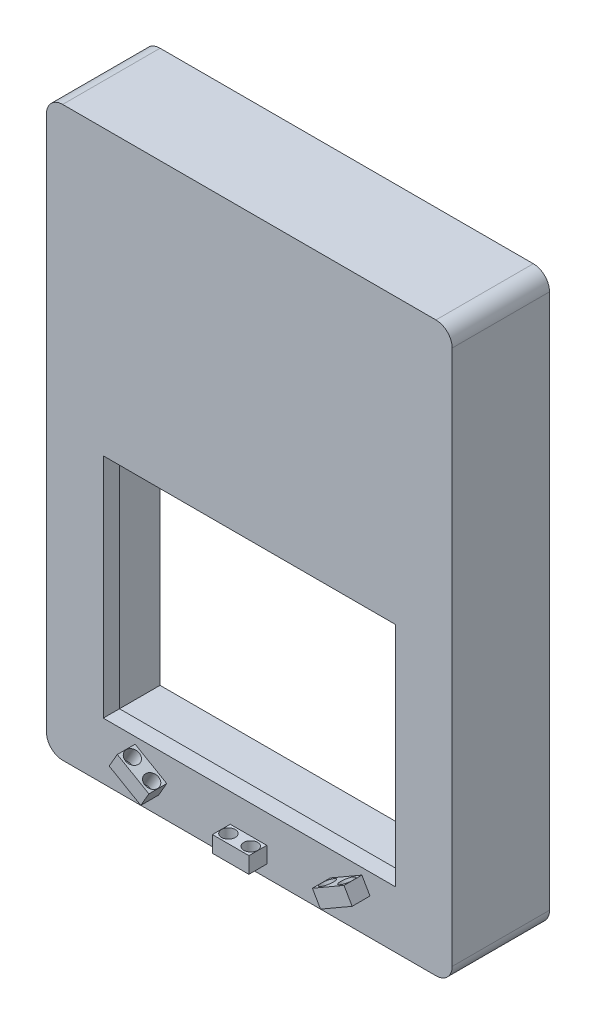
SolidWorks part; units mm, degrees
ref_plane "Piano frontale" through (0, 0, 0) normal (0, 0, 1) x (1, 0, 0)
ref_plane "Piano superiore" through (0, 0, 0) normal (0, 1, 0) x (1, 0, 0)
ref_plane "Piano destro" through (0, 0, 0) normal (1, 0, 0) x (0, 0, -1)
sketch "Schizzo1" plane through (0, 0, 0) normal (0, 0, 1) x (1, 0, 0)
  line L0 (0, 0) -> (0, -700)
  line L1 (0, 0) -> (500, 0)
  line L2 (500, 0) -> (500, -700)
  line L3 (500, -700) -> (0, -700)
  line L8 (20, -20) -> (480, -20)
  line L9 (480, -20) -> (480, -680)
  line L10 (480, -680) -> (20, -680)
  line L11 (20, -20) -> (20, -680)
  dimension "D1" = 700
  dimension "D2" = 500
  dimension "D3" = 20
extrude "Estrusione-Estrusione4" add sketch "Schizzo1" along normal blind 20 contours L3 L0 L1 L2
extrude "Estrusione-Estrusione5" add sketch "Schizzo1<4>" against normal blind 100
sketch "Schizzo1<4>" plane through (0, 0, 0) normal (0, 0, 1) x (1, 0, 0) same geometry as "Schizzo1"
sketch "Schizzo2" plane through (0, 0, 0) normal (0, 0, 1) x (1, 0, 0)
  line L4 (148.2503, -660.67) -> (138.2491, -677.9899)
  line L5 (226.5, -665) -> (271.5, -665)
  line L6 (226.5, -665) -> (226.5, -685)
  line L7 (226.5, -685) -> (271.5, -685)
  line L8 (271.5, -685) -> (271.5, -665)
  line L10 (109.2791, -638.17) -> (99.2791, -655.4905)
  line L11 (99.2791, -655.4905) -> (138.2491, -677.9899)
  line L14 (109.2791, -638.17) -> (148.2503, -660.67)
  line L21 (99.2791, -655.4905) -> (138.2491, -677.9899)
  line L23 (359.75, -677.9899) -> (398.7211, -655.4899)
  line L24 (388.7211, -638.1694) -> (398.7211, -655.4899)
  line L25 (349.75, -660.6694) -> (388.7211, -638.1694)
  line L28 (359.75, -677.9899) -> (349.75, -660.6694)
  dimension "D1" = 45
  dimension "D2" = 45
  dimension "D3" = 45
  dimension "D4" = 20
  dimension "D5" = 20
  dimension "D6" = 20
extrude "Estrusione-Estrusione6" add sketch "Schizzo2" along normal offset from surface (22 mm away) 22 from surface separate body contours L14 L10 L11 L4 | L7 L8 L5 L6 region at (123.7645, -658.0801, 0) region at (249, -675, 0) up to face at (250, -350, 20) offset beyond the face yes starting at face at (250, -350, 20)
extrude "Estrusione-Estrusione7" add sketch "Schizzo2<3>" along normal blind 22 from surface contours L23 L24 L25 L28 starting at face at (250, -350, 20)
sketch "Schizzo2<3>" plane through (0, 0, 0) normal (0, 0, 1) x (1, 0, 0) same geometry as "Schizzo2"
sketch "Schizzo6" plane through (-259.0159, -448.6288, 0) normal (-0.5, -0.866, 0) x (0.866, -0.5, 0)
  line L0 (436.2229, 42) -> (436.2229, 20) construction
  line L1 (458.7222, 42) -> (413.7235, 42) construction
  line L2 (413.7235, 20) -> (458.7222, 20) construction
  line L3 (422.4729, 31) -> (449.9729, 31) construction
  circle A0 centre (422.4729, 31) radius 8.5
  circle A1 centre (449.9729, 31) radius 8.5
  point P9 (436.2229, 31)
extrude "Taglio-Estrusione1" cut sketch "Schizzo6" against normal blind 22
sketch "Schizzo7" plane through (0, -685, 0) normal (0, -1, 0) x (1, 0, 0)
  line L0 (249, 42) -> (249, 20) construction
  line L1 (271.5, 42) -> (226.5, 42) construction
  line L2 (226.5, 20) -> (271.5, 20) construction
  line L3 (235.25, 31) -> (262.75, 31) construction
  circle A0 centre (235.25, 31) radius 8.5
  circle A1 centre (262.75, 31) radius 8.5
  point P9 (249, 31)
extrude "Taglio-Estrusione2" cut sketch "Schizzo7" against normal blind 22
sketch "Schizzo8" plane through (383.5157, -664.2687, 0) normal (0.5, -0.866, 0) x (0.866, 0.5, 0)
  line L0 (-4.9423, 42) -> (-4.9423, 20) construction
  line L1 (-27.4423, 42) -> (17.5577, 42) construction
  line L2 (-27.4423, 20) -> (17.5577, 20) construction
  line L3 (-18.6923, 31) -> (8.8077, 31) construction
  circle A0 centre (-18.6923, 31) radius 8.5
  circle A2 centre (8.8077, 31) radius 8.5
  point P9 (-4.9423, 31)
extrude "Taglio-Estrusione3" cut sketch "Schizzo8" against normal blind 22
sketch "Schizzo10" plane through (0, 0, 20) normal (0, 0, 1) x (1, 0, 0)
  line L10 (70, -350) -> (430, -350)
  line L14 (70, -630) -> (430, -630)
  line L15 (430, -630) -> (430, -70)
  line L16 (70, -70) -> (70, -630)
  line L17 (430, -70) -> (70, -70)
  line L18 (70, -630) -> (430, -630)
  line L19 (430, -630) -> (430, -350)
  line L20 (70, -350) -> (70, -630)
  dimension "D2" = 360
  dimension "D3" = 560
  dimension "D1" = 70
extrude "Taglio-Estrusione4" cut sketch "Schizzo10" against normal blind 22
fillet "Raccordo1" radius 20 1 edges at (0, 0, -40) type face fillet first side face at (250, 0, -40) second side face at (0, -350, -40)
fillet "Raccordo2" radius 20 1 edges at (500, 0, -40) type face fillet first side face at (260, 0, -40) second side face at (500, -350, -40)
fillet "Raccordo3" radius 20 1 edges at (500, -700, -40) type face fillet first side face at (500, -360, -40) second side face at (250, -700, -40)
fillet "Raccordo4" radius 20 1 edges at (0, -700, -40) type face fillet first side face at (0, -360, -40) second side face at (240, -700, -40)
